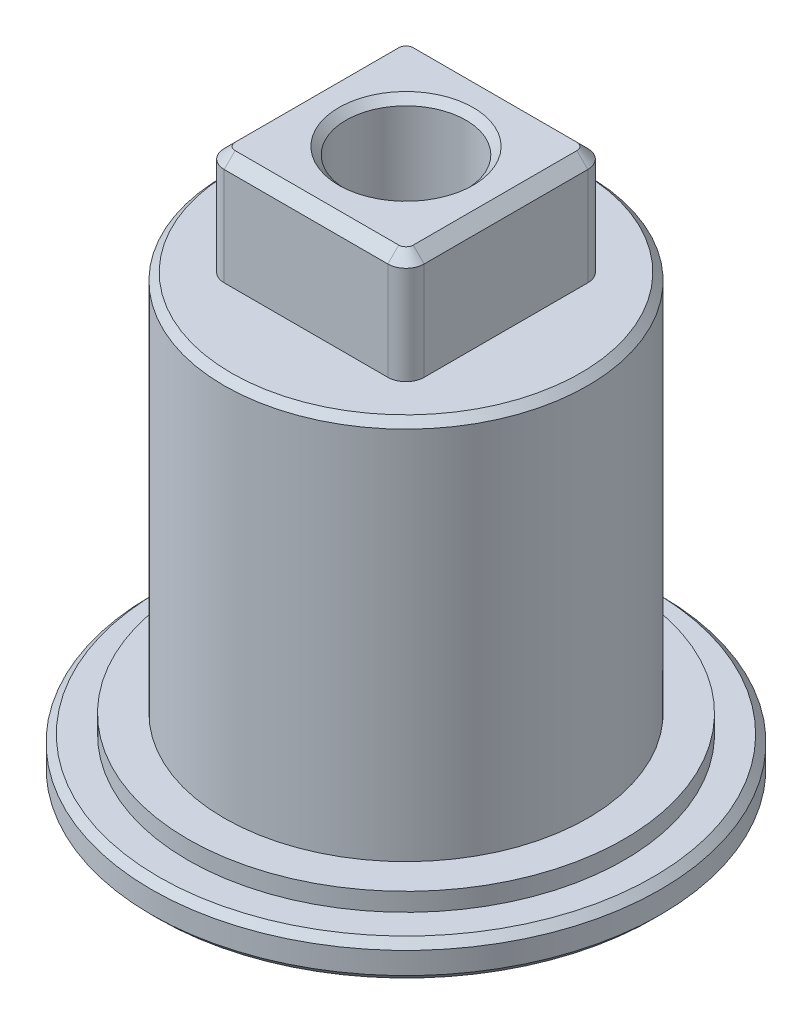
SolidWorks part; units mm, degrees
material "보통 탄소강"
ref_plane "정면" through (0, 0, 0) normal (0, 0, 1) x (1, 0, 0)
ref_plane "윗면" through (0, 0, 0) normal (0, 1, 0) x (1, 0, 0)
ref_plane "우측면" through (0, 0, 0) normal (1, 0, 0) x (0, 0, -1)
sketch "스케치1" plane through (0, 0, 0) normal (0, 1, 0) x (1, 0, 0)
  line L1 (-2.75, -2.75) -> (2.75, -2.75)
  line L2 (-2.75, -2.75) -> (-2.75, 2.75)
  line L3 (-2.75, 2.75) -> (2.75, 2.75)
  line L4 (2.75, -2.75) -> (2.75, 2.75)
  line L5 (-2.75, -2.75) -> (2.75, 2.75) construction
  line L6 (-2.75, 2.75) -> (2.75, -2.75) construction
  circle A0 centre (0, 0) radius 7
  circle A1 centre (0, 0) radius 6
  circle A2 centre (0, 0) radius 5
  circle A3 centre (0, 0) radius 4.25
  circle A5 centre (0, 0) radius 1.65
  dimension "D1" = 14
  dimension "D2" = 12
  dimension "D3" = 10
  dimension "D4" = 8.5
  dimension "D5" = 5.5
  dimension "D6" = 3.3
  dimension "D7" = 5.5
extrude "보스-돌출1" add sketch "스케치1" along normal blind 1 contours A0 A1 | A1 A2 | A2 A3 | A3 | A5 region at (-2.6722, 0, 0) region at (-6.802, 0, 0) region at (-5.8303, 0, 0) region at (-4.8586, 0, 0) region at (-4.1298, 0, 0)
extrude "보스-돌출2" add sketch "스케치1<4>" along normal blind 1.5 contours A1 A2 | A2 A3 | A3 | A5 region at (-2.6722, 0, 0) region at (-5.8303, 0, 0) region at (-4.8586, 0, 0) region at (-4.1298, 0, 0)
sketch "스케치1<4>" plane through (0, 0, 0) normal (0, 1, 0) x (1, 0, 0) same geometry as "스케치1"
extrude "보스-돌출3" add sketch "스케치1<5>" along normal blind 12 contours A2 A3 | A3 | A5 region at (-2.6722, 0, 0) region at (-4.8586, 0, 0) region at (-4.1298, 0, 0)
sketch "스케치1<5>" plane through (0, 0, 0) normal (0, 1, 0) x (1, 0, 0) same geometry as "스케치1"
extrude "보스-돌출4" add sketch "스케치1<6>" along normal blind 10 from offset 2 contours A3 region at (-4.1298, 0, 0)
sketch "스케치1<6>" plane through (0, 0, 0) normal (0, 1, 0) x (1, 0, 0) same geometry as "스케치1"
extrude "보스-돌출5" add sketch "스케치1<7>" along normal blind 13 from offset 2 contours A5 region at (-2.6722, 0, 0)
sketch "스케치1<7>" plane through (0, 0, 0) normal (0, 1, 0) x (1, 0, 0) same geometry as "스케치1"
extrude "보스-돌출6" add sketch "스케치1<8>" along normal blind 2 contours A5 region at (0, 0, 0)
sketch "스케치1<8>" plane through (0, 0, 0) normal (0, 1, 0) x (1, 0, 0) same geometry as "스케치1"
sketch "스케치2" plane through (0, 0, 0) normal (0, -1, 0) x (1, 0, 0)
  line L1 (-1, -4) -> (1, -4)
  line L2 (-1, -4) -> (-1, 4)
  line L3 (-1, 4) -> (1, 4)
  line L4 (1, -4) -> (1, 4)
  line L5 (-1, -4) -> (1, 4) construction
  line L6 (-1, 4) -> (1, -4) construction
  circle A0 centre (0, 3) radius 1
  circle A1 centre (0, -3) radius 1
  point P0 (0, 0)
  dimension "D1" = 8
  dimension "D2" = 2
extrude "컷-돌출1" cut sketch "스케치2" against normal blind 2 contours A1 | A1 L4 A0 L2 | A0 region at (0, 0, -3) region at (0, 0, 0) region at (0, 0, 3)
fillet "필렛1" radius 0.5 4 edges at (2.75, 13.5, 2.75) (2.75, 13.5, -2.75) (-2.75, 13.5, -2.75) (-2.75, 13.5, 2.75)
chamfer "모따기1" distance 0.2 angle 45 4 edges at (0, 12, 5) (0, 1, 7) (0, 0, 7) (0, 15, 1.65)
chamfer "모따기2" distance 0.3 angle 45 8 edges at (2.75, 15, 0) (0, 15, 2.75) (-2.75, 15, 0) (0, 15, -2.75) (-2.6036, 15, 2.6036) (2.6036, 15, 2.6036) (-2.6036, 15, -2.6036) (2.6036, 15, -2.6036)
sketch "스케치3" plane through (0, 0, 0) normal (1, 0, 0) x (0, 0, -1)
  line L0 (0, 2) -> (-1.65, 2)
  line L1 (-1.65, 2) -> (0, 1.3165)
  line L2 (0, 11.8) -> (0, 2)
  line L3 (-5, 11.8) -> (5, 11.8) construction
  line L5 (0, 2) -> (0, 1.3165)
  line L7 (1.3124, 2) -> (-1.3124, 2) construction
  dimension "D1" = 67.5
  dimension "D2" = 1.65
revolve "컷-회전1" cut sketch "스케치3" angle 360 about L2 region at (0, 1.7722, 0.55)
